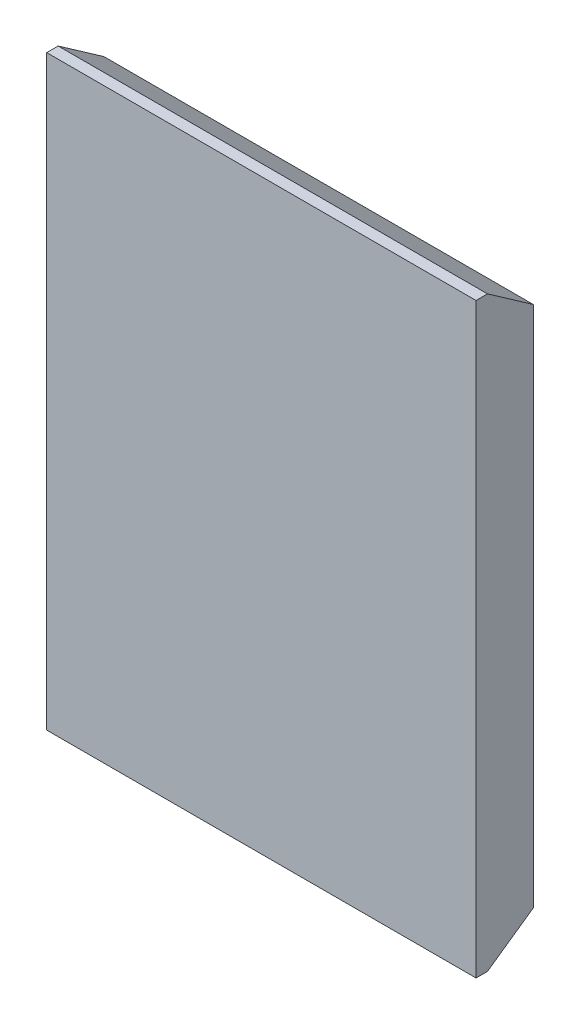
SolidWorks part; units mm, degrees
note: The reader was unsure of these and kept them because the rebuilt part matched: thickness of "基体-法兰1", "钣金6".
ref_plane "前视基准面" through (0, 0, 0) normal (0, 0, 1) x (1, 0, 0)
ref_plane "上视基准面" through (0, 0, 0) normal (0, 1, 0) x (1, 0, 0)
ref_plane "右视基准面" through (0, 0, 0) normal (1, 0, 0) x (0, 0, -1)
sketch "草图1" plane through (0, 0, 0) normal (0, 0, 1) x (1, 0, 0)
  line L1 (-75, 102.5) -> (75, 102.5)
  line L2 (-75, 102.5) -> (-75, -102.5)
  line L3 (-75, -102.5) -> (75, -102.5)
  line L4 (75, 102.5) -> (75, -102.5)
  line L5 (-75, 102.5) -> (75, -102.5) construction
  line L6 (-75, -102.5) -> (75, 102.5) construction
  point P0 (0, 0)
  dimension "D1" = 150
  dimension "D2" = 205
base flange "基体-法兰1" sketch "草图1" thickness 20 reverse thickness direction no parameters "D1"=1
chamfer "倒角1" distance 16 angle 35 1 edges at (0, 102.5, -20) first distance on face at (0, 102.5, -10)
chamfer "倒角2" distance 16 angle 35 1 edges at (0, -102.5, -20) first distance on face at (0, -102.5, -10)
sketch "折弯-线1" plane through (0, 0, 0) normal (0, 1, 0) x (1, 0, 0)
sketch "边界框1" plane through (0, 0, 0) normal (0, 1, 0) x (1, 0, 0)
sheet metal parameters "钣金6" thickness 20 parameters "D1"=1, "D7"=10
flat pattern "平板型式6" [suppressed]
sketch "折弯-线2" plane through (0, 0, 0) normal (0, 1, 0) x (1, 0, 0)
sketch "边界框2" [suppressed] plane through (0, 0, 0) normal (0, 1, 0) x (1, 0, 0)
